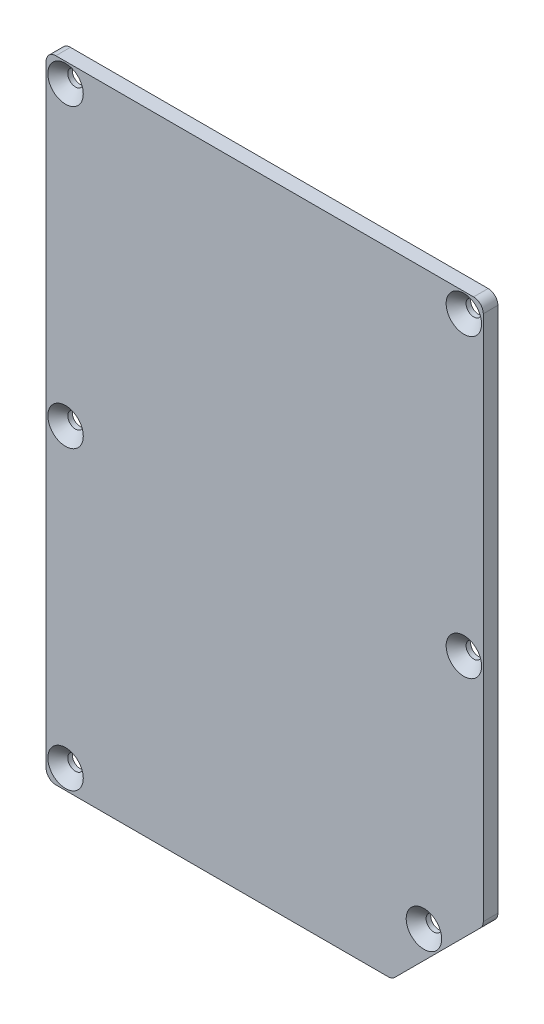
SolidWorks part; units mm, degrees
ref_plane "Front Plane" through (0, 0, 0) normal (0, 0, 1) x (1, 0, 0)
ref_plane "Top Plane" through (0, 0, 0) normal (0, 1, 0) x (1, 0, 0)
ref_plane "Right Plane" through (0, 0, 0) normal (1, 0, 0) x (0, 0, -1)
sketch "Sketch1" plane through (0, 0, 0) normal (0, 0, 1) x (1, 0, 0)
  line B0 (-43, 70) -> (43, 70)
  line B1 (-45, 68) -> (-45, -58)
  line B2 (-43, -60) -> (25.3848, -60)
  line B3 (45, 68) -> (45, -40.3848)
  line B4 (44.4142, -41.799) -> (26.799, -59.4142)
  arc B5 (-43, -60) -> (-45, -58) centre (-43, -58) cw
  arc B6 (45, 68) -> (43, 70) centre (43, 68) ccw
  arc B7 (-43, 70) -> (-45, 68) centre (-43, 68) ccw
  arc B8 (45, -40.3848) -> (44.4142, -41.799) centre (43, -40.3848) cw
  arc B9 (26.799, -59.4142) -> (25.3848, -60) centre (25.3848, -58) cw
sketch_block_instance "Block-B01_block_lid-1"
sketch_block "Block-B01_block_lid"
extrude "Boss-Extrude1" add sketch "Sketch1" along normal blind 3
sketch "Sketch5" plane through (0, 0, 3) normal (0, 0, 1) x (1, 0, 0)
  point P0 (-41, 66)
  point P1 (41, 66)
  point P3 (41, 5)
  point P5 (32.7782, -47.7782)
  point P7 (-41, -56)
  point P9 (-41, 5)
  point P11 (-41, 66)
hole_wizard "CSK for M3 Countersunk Flat Head Screw1" positions "3DSketch3" profile "Sketch6" countersink size "M3" standard "ISO"
sketch3d "3DSketch3"
  point P0 (-41, -56, 3)
  point P3 (32.7782, -47.7782, 3)
  point P6 (41, 5, 3)
  point P9 (-41, 5, 3)
  point P12 (-41, 66, 3)
  point P15 (41, 66, 3)
sketch "Sketch6" plane through (-41, -56, 3) normal (1, 0, 0) x (0, -1, 0)
  line L0 (0, 0) -> (0, 5.9614)
  line L1 (0, 5.9614) -> (1.6, 5)
  line L2 (1.6, 5) -> (1.6, 2.05)
  line L3 (1.6, 2.05) -> (3.65, 0)
  line L5 (3.65, 0) -> (0, 0)
  line L6 (-1.6, 2.05) -> (-3.65, 0) construction
  line L10 (0, 5.9614) -> (-1.6, 5) construction
  line L11 (0, -6.35) -> (0, 107.95) construction
  dimension "Hole Dia." = 3.2
  dimension "Hole Depth" = 5
  dimension "Near C'Sink Dia." = 7.3
  dimension "Near C'Sink Angle" = 90
  dimension "Drill Angle" = 118
